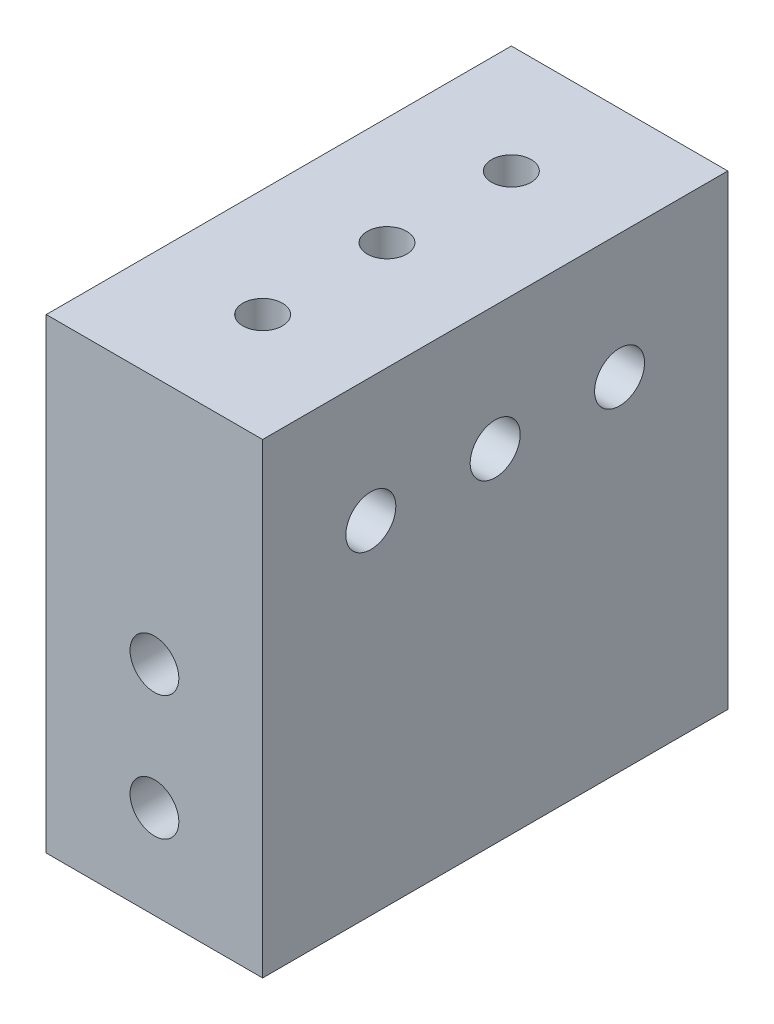
SolidWorks part; units mm, degrees
other "Markup1"
sketch "Sketch3" plane through (12.6365, 38.1, -23.749) normal (0.9027, 0.4189, -0.0984) x (-0.0151, -0.1977, -0.9801)
sketch "Sketch7" plane through (11.049, 23.8125, -23.749) normal (0.9027, 0.4189, -0.0984) x (-0.0151, -0.1977, -0.9801)
sketch "Sketch9" plane through (11.049, 23.8125, -23.749) normal (0.9027, 0.4189, -0.0984) x (-0.0151, -0.1977, -0.9801)
other "Markup2"
sketch "Sketch4" plane through (12.6365, 38.1, -23.749) normal (0.9027, 0.4189, -0.0984) x (-0.0151, -0.1977, -0.9801)
sketch "Sketch8" plane through (11.049, 23.8125, -23.749) normal (0.9027, 0.4189, -0.0984) x (-0.0151, -0.1977, -0.9801)
sketch "Sketch10" plane through (11.049, 23.8125, -23.749) normal (0.9027, 0.4189, -0.0984) x (-0.0151, -0.1977, -0.9801)
other "Markup3"
sketch "Sketch11" plane through (11.049, 23.8125, -23.749) normal (1, 0.0033, -0.0037) x (-0.003, -0.1893, -0.9819)
material "6061-T6 (SS)"
ref_plane "Front Plane" through (0, 0, 0) normal (0, 0, 1) x (1, 0, 0)
ref_plane "Top Plane" through (0, 0, 0) normal (0, 1, 0) x (1, 0, 0)
ref_plane "Right Plane" through (0, 0, 0) normal (1, 0, 0) x (0, 0, -1)
sketch "Sketch1" plane through (0, 0, 0) normal (0, 1, 0) x (1, 0, 0)
  line L0 (-12.6365, 25.3365) -> (12.6365, 25.3365)
  line L1 (-11.049, -23.749) -> (11.049, -23.749)
  line L2 (-11.049, -23.749) -> (-11.049, 23.749)
  line L3 (-11.049, 23.749) -> (11.049, 23.749)
  line L4 (11.049, -23.749) -> (11.049, 23.749)
  line L5 (-11.049, -23.749) -> (11.049, 23.749) construction
  line L6 (-11.049, 23.749) -> (11.049, -23.749) construction
  line L7 (12.6365, -25.3365) -> (12.6365, 25.3365)
  line L8 (-12.6365, -25.3365) -> (12.6365, -25.3365)
  line L9 (-12.6365, -25.3365) -> (-12.6365, 25.3365)
  point P0 (0, 0)
  dimension "D1" = 22.098
  dimension "D2" = 47.498
  dimension "D3" = 1.5875
extrude "Boss-Extrude1" add sketch "Sketch1" along normal mid plane 47.625 contours L1 L4 L3 L2 region at (0, 0, 0)
sketch "Sketch2" plane through (11.049, 0, 0) normal (1, 0, 0) x (0, 0, -1)
  line L0 (-23.749, 23.8125) -> (23.749, 23.8125) construction
  line L4 (-25.4, -23.8125) -> (25.4, -23.8125) construction
  line L5 (-25.4, -23.8125) -> (-25.4, 23.8125) construction
  line L6 (-25.4, 23.8125) -> (25.4, 23.8125) construction
  line L7 (25.4, -23.8125) -> (25.4, 23.8125) construction
  line L8 (-25.4, -23.8125) -> (25.4, 23.8125) construction
  line L9 (-25.4, 23.8125) -> (25.4, -23.8125) construction
  circle A0 centre (-12.7, 11.1125) radius 2.5527
  circle A1 centre (0, 11.1125) radius 2.5527
  circle A2 centre (12.7, 11.1125) radius 2.5527
  point P6 (0, 0)
  dimension "D1" = 5.1054
  dimension "D2" = 50.8
  dimension "D4" = 25.4
  dimension "D5" = 12.7
  dimension "D6" = 38.1
  dimension "D7" = 12.7
  dimension "D8" = 12.7
  dimension "D9" = 12.7
extrude "Cut-Extrude1" cut sketch "Sketch2" against normal through all
sketch "Sketch5" plane through (0, 0, -23.749) normal (0, 0, -1) x (-1, 0, 0)
  line L0 (11.049, 23.8125) -> (-11.049, 23.8125) construction
  line L1 (-12.7, -23.8125) -> (12.7, -23.8125) construction
  line L2 (-12.7, -23.8125) -> (-12.7, 23.8125) construction
  line L3 (-12.7, 23.8125) -> (12.7, 23.8125) construction
  line L4 (12.7, -23.8125) -> (12.7, 23.8125) construction
  line L5 (-12.7, -23.8125) -> (12.7, 23.8125) construction
  line L6 (-12.7, 23.8125) -> (12.7, -23.8125) construction
  circle A0 centre (0, -1.5875) radius 2.4892
  circle A2 centre (0, -14.2875) radius 2.4892
  point P0 (0, 0)
  dimension "D5" = 38.1
  dimension "D7" = 4.9784
  dimension "D8" = 4.9784
  dimension "D1" = 25.4
  dimension "D3" = 25.4
  dimension "D4" = 12.7
  dimension "D6" = 12.7
extrude "Cut-Extrude2" cut sketch "Sketch5" against normal through all
sketch "Sketch6" plane through (0, 23.8125, 0) normal (0, 1, 0) x (1, 0, 0)
  line L1 (11.049, -23.749) -> (11.049, 23.749) construction
  circle A0 centre (0, 0) radius 2.0193
  circle A1 centre (0, 12.7) radius 2.0193
  circle A2 centre (0, -12.7) radius 2.0193
  dimension "D3" = 4.0386
  dimension "D1" = 12.7
  dimension "D2" = 12.7
  dimension "D4" = 11.049
  dimension "D5" = 11.049
extrude "Cut-Extrude3" cut sketch "Sketch6" against normal blind 6.35
